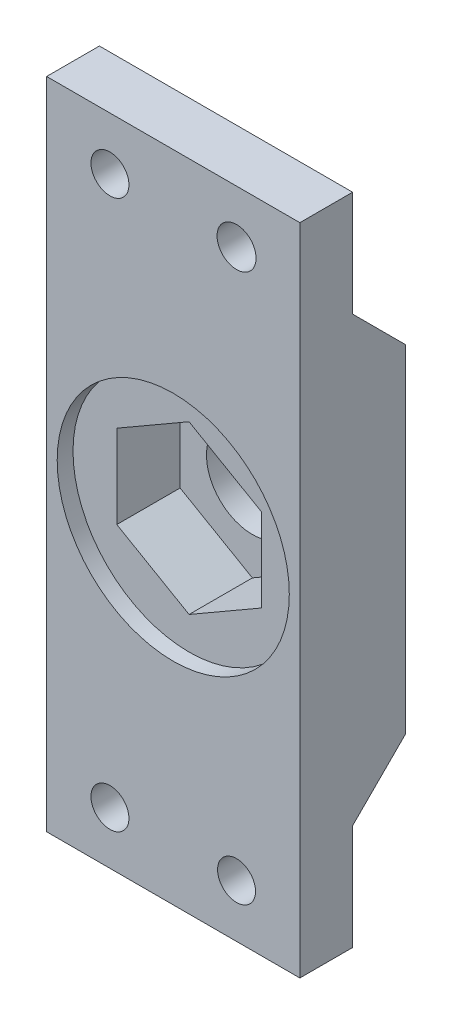
SolidWorks part; units mm, degrees
ref_plane "Plano frontal" through (0, 0, 0) normal (0, 0, 1) x (1, 0, 0)
ref_plane "Plano superior" through (0, 0, 0) normal (0, 1, 0) x (1, 0, 0)
ref_plane "Plano direito" through (0, 0, 0) normal (1, 0, 0) x (0, 0, -1)
sketch "Esboço1" plane through (0, 0, 0) normal (0, 0, 1) x (1, 0, 0)
  line L1 (-12, 31) -> (12, 31)
  line L2 (-12, 31) -> (-12, -31)
  line L3 (-12, -31) -> (12, -31)
  line L4 (12, 31) -> (12, -31)
  line L5 (-12, 31) -> (12, -31) construction
  line L6 (-12, -31) -> (12, 31) construction
  point P0 (0, 0)
extrude "Ressalto-extrusão1" add sketch "Esboço1" along normal blind 10
sketch "Esboço4" plane through (0, 0, 10) normal (0, 0, -1) x (-1, 0, 0)
  circle A0 centre (0, 0) radius 11
extrude "Corte-extrusão1" cut sketch "Esboço4" along normal blind 1.5
sketch "Esboço6" plane through (0, 0, 8.5) normal (0, 0, 1) x (1, 0, 0)
  line L1 (0, -7.9097) -> (6.85, -3.9548)
  line L2 (6.85, -3.9548) -> (6.85, 3.9548)
  line L3 (6.85, 3.9548) -> (0, 7.9097)
  line L4 (0, 7.9097) -> (-6.85, 3.9548)
  line L5 (-6.85, 3.9548) -> (-6.85, -3.9548)
  line L6 (-6.85, -3.9548) -> (0, -7.9097)
  circle A0 centre (0, 0) radius 6.85 construction
extrude "Corte-extrusão2" cut sketch "Esboço6" against normal blind 6
sketch "Esboço9" plane through (0, 0, 10) normal (0, 0, 1) x (1, 0, 0)
  line L0 (0, 31) -> (0, 26) construction
  line L1 (12, 31) -> (-12, 31) construction
  line L2 (0, -31) -> (0, -26) construction
  line L3 (-12, -31) -> (12, -31) construction
  line L4 (0, 26) -> (6, 26) construction
  line L5 (6, 26) -> (-6, 26) construction
  line L6 (-6, 26) -> (-6, -26) construction
  line L7 (-6, -26) -> (6, -26) construction
  circle A0 centre (0, 0) radius 4.35
  circle A1 centre (6, 26) radius 1.85
  circle A2 centre (-6, 26) radius 1.8
  circle A3 centre (-6, -26) radius 1.8
  circle A4 centre (6, -26) radius 1.8
extrude "Corte-extrusão4" cut sketch "Esboço9" against normal through all
sketch "Esboço11" plane through (-12, 0, 0) normal (-1, 0, 0) x (0, 0, 1)
  line L0 (5.0046, -21) -> (5, -31)
  line L1 (0, 31) -> (0, -31) construction
  line L2 (10, -31) -> (0, -31) construction
  line L3 (5, -31) -> (10, -31)
  line L4 (5.0046, -21) -> (0, -15.9954)
  line L5 (0, 15.9954) -> (0, -15.9954)
  line L6 (0, 0) -> (10, 0) construction
  line L8 (10, 31) -> (10, -31)
  line L9 (5.0046, 21) -> (0, 15.9954)
  line L10 (5, 31) -> (10, 31)
  line L11 (5.0046, 21) -> (5, 31)
extrude "Corte-extrusão7" cut sketch "Esboço11" against normal through all flip side to cut
sketch "Esboço12" plane through (0, 0.0023, 5.0141) normal (0, -0.0005, -1) x (-1, 0, 0)
  line L0 (11.7, 21.2977) -> (11.7, 30.6977)
  line L1 (11.7, 30.6977) -> (-11.7, 30.6977)
  line L2 (-11.7, 30.6977) -> (-11.7, 21.2977)
  line L3 (-11.7, 21.2977) -> (11.7, 21.2977)
  line L4 (12, 20.9977) -> (12, 30.9977)
  line L5 (12, 30.9977) -> (-12, 30.9977)
  line L6 (-12, 30.9977) -> (-12, 20.9977)
  line L7 (-12, 20.9977) -> (12, 20.9977)
  line L8 (12, 20.9977) -> (12, 30.9977)
  line L9 (12, 30.9977) -> (-12, 30.9977)
  line L10 (-12, 30.9977) -> (-12, 20.9977)
  line L11 (-12, 20.9977) -> (12, 20.9977)
  line L12 (0, 0) -> (11.7, 0) construction
  line L13 (-12, -20.9977) -> (12, -20.9977)
  line L14 (-12, -30.9977) -> (-12, -20.9977)
  line L15 (12, -30.9977) -> (-12, -30.9977)
  line L16 (12, -20.9977) -> (12, -30.9977)
  line L17 (-11.7, -21.2977) -> (11.7, -21.2977)
  line L18 (-11.7, -30.6977) -> (-11.7, -21.2977)
  line L19 (11.7, -30.6977) -> (-11.7, -30.6977)
  line L20 (11.7, -21.2977) -> (11.7, -30.6977)
  circle A0 centre (-6, 25.9977) radius 1.85 construction
  circle A1 centre (6, 25.9977) radius 1.8 construction
  circle A2 centre (-6, 25.9977) radius 1.85
  circle A3 centre (6, 25.9977) radius 1.8
  circle A4 centre (-6, 25.9977) radius 2.15
  circle A5 centre (6, 25.9977) radius 2.1
  circle A6 centre (6, -25.9977) radius 2.1
  circle A7 centre (-6, -25.9977) radius 2.15
  circle A8 centre (6, -25.9977) radius 1.8
  circle A9 centre (-6, -25.9977) radius 1.85
  ellipse M5 centre (6, 25.9977) end of major axis (6, 24.1977) minor radius 1.8
  line M6 (12, 20.9977) -> (12, 30.9977)
  line M7 (12, 30.9977) -> (-12, 30.9977)
  line M8 (-12, 30.9977) -> (-12, 20.9977)
  line M9 (-12, 20.9977) -> (12, 20.9977)
  ellipse M10 centre (-6, 25.9977) end of major axis (-6, 24.1477) minor radius 1.85
  dimension "D1" = 0
  dimension "D2" = 0.3
  dimension "D3" = 0.3
extrude "suporte" [suppressed] add sketch "Esboço12" along normal up to surface (5.0013 mm away) contours A4 M10 | L3 L2 L1 L0 M9 M6 M7 M8 | A5 M5 | A7 A9 | L16 L13 L14 L15 L17 L20 L19 L18 | A6 A8 up to face at (4.35, 0, 0)
